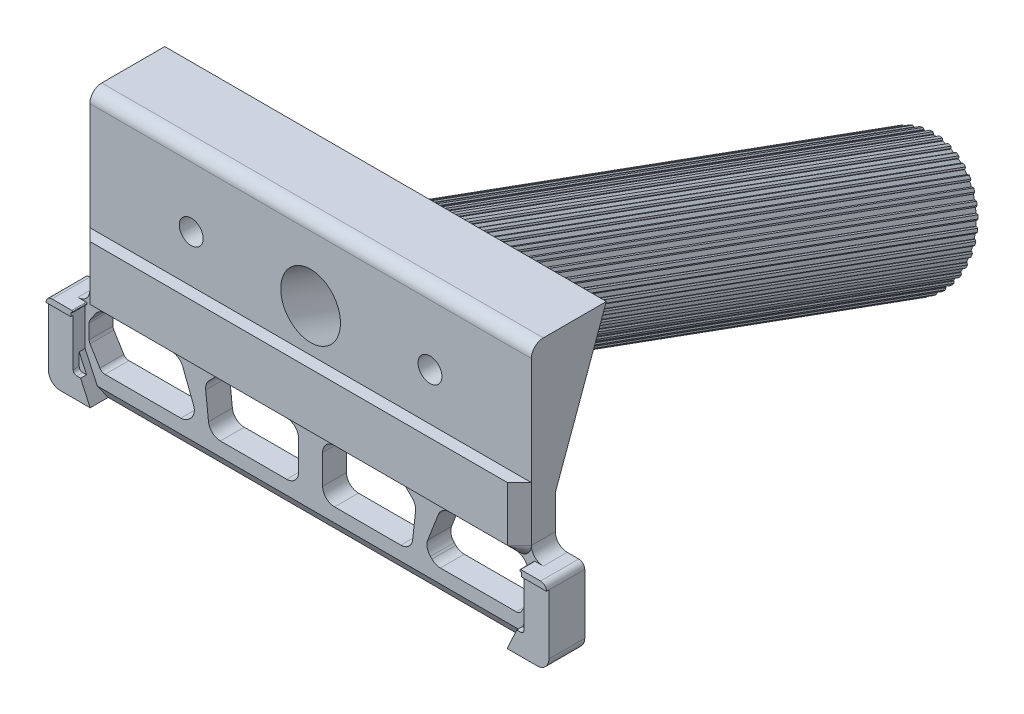
SolidWorks part; units mm, degrees
ref_plane "Front Plane" through (0, 0, 0) normal (0, 0, 1) x (1, 0, 0)
ref_plane "Top Plane" through (0, 0, 0) normal (0, 1, 0) x (1, 0, 0)
ref_plane "Right Plane" through (0, 0, 0) normal (1, 0, 0) x (0, 0, -1)
sketch "base plate" plane through (0, 0, 0) normal (0, 0, 1) x (1, 0, 0)
  line L0 (19.4937, 6.5) -> (20.4641, 6.5)
  line L1 (-18.4937, 12.0545) -> (-18.4937, 7.5)
  line L2 (20.9641, 6) -> (20.9641, 1)
  line L3 (19.9641, 0) -> (-19.9641, 0)
  line L4 (2.0062, 6.5) -> (7.9562, 6.5)
  line L5 (18.0111, 6.0574) -> (18.4651, 5.381)
  line L7 (18.4761, 3.6343) -> (17.6502, 2.2885)
  line L9 (18.4937, 7.5) -> (18.4937, 12.0545)
  line L10 (18.4937, 12.0545) -> (-18.4937, 12.0545)
  line L12 (18.55, 5.1023) -> (18.55, 3.8958)
  line L13 (7.558, 2.05) -> (2.0062, 2.05)
  line L14 (11.6407, 6.5) -> (17.1808, 6.5)
  line L16 (1.0062, 5.5) -> (1.0062, 3.05)
  line L21 (7.9562, 6.5) -> (8.5017, 5.9545)
  line L22 (8.7888, 5.1403) -> (8.5523, 2.943)
  line L23 (10.8704, 2.05) -> (17.2241, 2.05)
  line L24 (10.1633, 2.3429) -> (10.0333, 2.4728)
  line L25 (9.8082, 3.5417) -> (10.7085, 5.8618)
  line L31 (-9.8082, 3.5417) -> (-10.7085, 5.8618)
  line L33 (18.4937, 12.0545) -> (18.4937, 7.5)
  line L36 (-10.1633, 2.3429) -> (-10.0333, 2.4728)
  line L43 (0, 12.0545) -> (0, 0) construction
  line L44 (-10.8704, 2.05) -> (-17.2241, 2.05)
  line L45 (-8.7888, 5.1403) -> (-8.5523, 2.943)
  line L46 (-7.9562, 6.5) -> (-8.5017, 5.9545)
  line L47 (-1.0062, 5.5) -> (-1.0062, 3.05)
  line L48 (-11.6407, 6.5) -> (-17.1808, 6.5)
  line L49 (-7.558, 2.05) -> (-2.0062, 2.05)
  line L50 (-18.55, 5.1023) -> (-18.55, 3.8958)
  line L51 (-18.4937, 7.5) -> (-18.4937, 12.0545)
  line L52 (-18.4761, 3.6343) -> (-17.6502, 2.2885)
  line L53 (-18.0111, 6.0574) -> (-18.4651, 5.381)
  line L54 (-2.0062, 6.5) -> (-7.9562, 6.5)
  line L55 (-20.9641, 6) -> (-20.9641, 1)
  line L56 (-19.4937, 6.5) -> (-20.4641, 6.5)
  arc A0 (18.4937, 7.5) -> (19.4937, 6.5) centre (19.4937, 7.5) ccw
  arc A2 (17.2241, 2.05) -> (17.6502, 2.2885) centre (17.2241, 2.55) ccw
  arc A3 (18.4761, 3.6343) -> (18.55, 3.8958) centre (18.05, 3.8958) ccw
  arc A4 (18.4651, 5.381) -> (18.55, 5.1023) centre (18.05, 5.1023) cw
  arc A5 (20.9641, 6) -> (20.4641, 6.5) centre (20.4641, 6) ccw
  arc A6 (19.9641, 0) -> (20.9641, 1) centre (19.9641, 1) ccw
  arc A7 (7.558, 2.05) -> (8.5523, 2.943) centre (7.558, 3.05) ccw
  arc A8 (8.7888, 5.1403) -> (8.5017, 5.9545) centre (7.7946, 5.2474) ccw
  arc A9 (10.0333, 2.4728) -> (9.8082, 3.5417) centre (10.7404, 3.1799) cw
  arc A10 (10.1633, 2.3429) -> (10.8704, 2.05) centre (10.8704, 3.05) ccw
  arc A11 (11.6407, 6.5) -> (10.7085, 5.8618) centre (11.6407, 5.5) ccw
  arc A12 (2.0062, 2.05) -> (1.0062, 3.05) centre (2.0062, 3.05) cw
  arc A13 (2.0062, 6.5) -> (1.0062, 5.5) centre (2.0062, 5.5) ccw
  arc A29 (18.0111, 6.0574) -> (17.1808, 6.5) centre (17.1808, 5.5) ccw
  arc A30 (-18.0111, 6.0574) -> (-17.1808, 6.5) centre (-17.1808, 5.5) cw
  arc A31 (-2.0062, 6.5) -> (-1.0062, 5.5) centre (-2.0062, 5.5) cw
  arc A32 (-2.0062, 2.05) -> (-1.0062, 3.05) centre (-2.0062, 3.05) ccw
  arc A33 (-11.6407, 6.5) -> (-10.7085, 5.8618) centre (-11.6407, 5.5) cw
  arc A34 (-10.1633, 2.3429) -> (-10.8704, 2.05) centre (-10.8704, 3.05) cw
  arc A35 (-10.0333, 2.4728) -> (-9.8082, 3.5417) centre (-10.7404, 3.1799) ccw
  arc A36 (-8.7888, 5.1403) -> (-8.5017, 5.9545) centre (-7.7946, 5.2474) cw
  arc A37 (-7.558, 2.05) -> (-8.5523, 2.943) centre (-7.558, 3.05) cw
  arc A38 (-19.9641, 0) -> (-20.9641, 1) centre (-19.9641, 1) cw
  arc A39 (-20.9641, 6) -> (-20.4641, 6.5) centre (-20.4641, 6) cw
  arc A40 (-18.4651, 5.381) -> (-18.55, 5.1023) centre (-18.05, 5.1023) ccw
  arc A41 (-18.4761, 3.6343) -> (-18.55, 3.8958) centre (-18.05, 3.8958) cw
  arc A42 (-17.2241, 2.05) -> (-17.6502, 2.2885) centre (-17.2241, 2.55) cw
  arc A43 (-18.4937, 7.5) -> (-19.4937, 6.5) centre (-19.4937, 7.5) cw
  dimension "D3" = 4.45
  dimension "D7" = 0.5
  dimension "D6" = 20.9641
  dimension "D1" = 12.0545
  dimension "D2" = 2.05
  dimension "D4" = 6.5
  dimension "D8" = 0.4704
  dimension "D5" = 1
  dimension "D9" = 1
  dimension "D10" = 6.95
  dimension "D11" = 2.45
  dimension "D12" = 0.7715
  dimension "D16" = 10.8704
  dimension "D23" = 0.5
  dimension "D20" = 5.1023
  dimension "D13" = 7.9562
  dimension "D14" = 8.5017
  dimension "D15" = 8.5523
  dimension "D17" = 9.8082
  dimension "D18" = 3.5417
  dimension "D19" = 0.1838
  dimension "D21" = 3.6343
  dimension "D22" = 1.579
  dimension "D24" = 0.8146
  dimension "D25" = 18.0111
  dimension "D27" = 6.0574
extrude "Boss-Extrude3" add sketch "base plate" along normal blind 2 contours L3 A6 L2 A5 L0 A0 L9 L10 A29 L5 A4 L12 A3 L7 A2 L23 A10 L24 A9 L25 A11 L14 A13 L4 L21 A8 L22 A7 L13 A12 L16 | L43 L10 L1 A43 L56 A39 L55 A38 L3 L44 A42 L52 A41 L50 A40 L53 A30 L48 A33 L31 A35 L36 A34 L49 A37 L45 A36 L46 L54 A31 L47 A32 region at (10.051, 6.4857, 0) region at (-10.051, 6.4857, 0)
sketch "Sketch3" plane through (0, 0, 2) normal (0, 0, 1) x (1, 0, 0)
  line L16 (0, 0) -> (0, 12.0545) construction
  line L17 (18.4937, 12.0545) -> (-18.4937, 12.0545) construction
  line L18 (-18.4937, 12.0545) -> (18.4937, 12.0545)
  line L19 (18.4937, 12.0545) -> (18.4937, 7.5)
  line L20 (-17.4937, 6.5) -> (17.4937, 6.5)
  line L21 (2.0062, 6.5) -> (7.9562, 6.5) construction
  line L22 (-18.4937, 12.0545) -> (-18.4937, 7.5)
  arc A6 (17.4937, 6.5) -> (18.4937, 7.5) centre (17.4937, 7.5) ccw
  arc A7 (-17.4937, 6.5) -> (-18.4937, 7.5) centre (-17.4937, 7.5) cw
  point P16 (0, 6.5)
  dimension "D1" = 1
extrude "Boss-Extrude4" add sketch "Sketch3" along normal blind 1
sketch "pill" plane through (0, 0, 3) normal (0, 0, 1) x (1, 0, 0)
  line L14 (20.9641, 6) -> (18.8845, 6)
  line L19 (18.7281, 6.43) -> (18.7281, 6.4096)
  line L21 (18.7981, 6.3396) -> (18.8145, 6.3396)
  line L22 (19.4937, 6.5) -> (20.4641, 6.5) construction
  line L23 (18.7981, 6.5) -> (20.4641, 6.5)
  line L24 (18.8845, 6) -> (18.8845, 6.2696)
  line L26 (0, -1.1) -> (0, 1.1) construction
  line L27 (-18.8845, 6) -> (-18.8845, 6.2696)
  line L28 (-18.7981, 6.5) -> (-20.4641, 6.5)
  line L29 (-18.7981, 6.3396) -> (-18.8145, 6.3396)
  line L30 (-18.7281, 6.43) -> (-18.7281, 6.4096)
  line L31 (-20.9641, 6) -> (-18.8845, 6)
  arc A11 (18.7981, 6.5) -> (18.7281, 6.43) centre (18.7981, 6.43) ccw
  arc A12 (18.8145, 6.3396) -> (18.8845, 6.2696) centre (18.8145, 6.2696) cw
  arc A13 (18.7281, 6.4096) -> (18.7981, 6.3396) centre (18.7981, 6.4096) ccw
  arc A14 (20.9641, 6) -> (20.4641, 6.5) centre (20.4641, 6) ccw construction
  arc A15 (20.9641, 6) -> (20.4641, 6.5) centre (20.4641, 6) ccw
  arc A16 (-20.9641, 6) -> (-20.4641, 6.5) centre (-20.4641, 6) cw
  arc A17 (-18.7281, 6.4096) -> (-18.7981, 6.3396) centre (-18.7981, 6.4096) cw
  arc A18 (-18.8145, 6.3396) -> (-18.8845, 6.2696) centre (-18.8145, 6.2696) ccw
  arc A19 (-18.7981, 6.5) -> (-18.7281, 6.43) centre (-18.7981, 6.43) cw
  dimension "D4" = 0.0164
  dimension "D3" = 0.2696
  dimension "D1" = 0.07
  dimension "D2" = 18.7281
  dimension "D5" = 0.0204
extrude "pill extrude" add sketch "pill" against normal up to next and the other way blind 0.2 contours L21 | A19 L28 A16 L31 L27 A18 L29 A17 L30 region at (19.8486, 6.2466, 3) region at (-19.8486, 6.2466, 3)
sketch "pods" plane through (0, 0, 2) normal (0, 0, 1) x (1, 0, 0)
  line L2 (20.9641, 6) -> (18.8845, 6) construction
  line L6 (19.9641, 0) -> (-19.9641, 0) construction
  line L7 (20.9641, 6) -> (20.9641, 1) construction
  line L14 (20.9641, 6) -> (18.8845, 6)
  line L15 (19.9641, 0) -> (17.4641, 0)
  line L20 (20.9641, 6) -> (20.9641, 1)
  line L21 (18.8845, 6) -> (18.8845, 3.1)
  line L22 (18.8845, 3.1) -> (17.4641, 0)
  line L23 (0, 0) -> (0, 12.0545) construction
  line L24 (18.4937, 12.0545) -> (-18.4937, 12.0545) construction
  line L25 (-18.8845, 3.1) -> (-17.4641, 0)
  line L26 (-18.8845, 6) -> (-18.8845, 3.1)
  line L27 (-20.9641, 6) -> (-20.9641, 1)
  line L28 (-19.9641, 0) -> (-17.4641, 0)
  line L29 (-20.9641, 6) -> (-18.8845, 6)
  arc A0 (19.9641, 0) -> (20.9641, 1) centre (19.9641, 1) ccw construction
  arc A2 (19.9641, 0) -> (20.9641, 1) centre (19.9641, 1) ccw
  arc A3 (-19.9641, 0) -> (-20.9641, 1) centre (-19.9641, 1) cw
  dimension "D1" = 3.5
  dimension "D2" = 3.1
extrude "Boss-Extrude7" add sketch "pods" along normal blind 1 contours L15 A2 L20 L14 L21 L22 | A3 L28 L25 L26 L29 L27 region at (19.6819, 2.7419, 2) region at (-19.6819, 2.7419, 2)
sketch "Sketch6" plane through (0, 0, 0) normal (0, 0, 1) x (1, 0, 0)
  line L0 (-18.5845, 0) -> (18.5845, 0)
  line L1 (18.8845, 0.3) -> (18.8845, 6.2696)
  line L2 (18.7981, 6.5) -> (21.4, 6.5)
  line L3 (21.6, 6.7) -> (21.6, 10.8413)
  line L4 (21.6, 10.8413) -> (-21.6, 10.8413)
  line L5 (0, 10.8413) -> (0, 0) construction
  line L10 (18.7281, 6.43) -> (18.7281, 6.4096)
  line L11 (18.7981, 6.3396) -> (18.8145, 6.3396)
  line L12 (-18.7981, 6.3396) -> (-18.8145, 6.3396)
  line L13 (-18.7281, 6.43) -> (-18.7281, 6.4096)
  line L15 (-21.6, 6.7) -> (-21.6, 10.8413)
  line L16 (-18.7981, 6.5) -> (-21.4, 6.5)
  line L17 (-18.8845, 0.3) -> (-18.8845, 6.2696)
  line L18 (17.4641, 0) -> (-17.4641, 0) construction
  line L20 (-18.8845, 6) -> (-18.8845, 6.2696) construction
  line L21 (-18.7981, 6.5) -> (-20.4641, 6.5) construction
  line L22 (18.8845, 6) -> (18.8845, 6.2696) construction
  line L23 (-18.7281, 6.4096) -> (-18.7281, 6.43) construction
  arc A1 (18.5845, 0) -> (18.8845, 0.3) centre (18.5845, 0.3) ccw
  arc A2 (18.7981, 6.5) -> (18.7281, 6.43) centre (18.7981, 6.43) ccw
  arc A3 (18.8145, 6.3396) -> (18.8845, 6.2696) centre (18.8145, 6.2696) cw
  arc A4 (18.7281, 6.4096) -> (18.7981, 6.3396) centre (18.7981, 6.4096) ccw
  arc A5 (21.4, 6.5) -> (21.6, 6.7) centre (21.4, 6.7) ccw
  arc A6 (-21.4, 6.5) -> (-21.6, 6.7) centre (-21.4, 6.7) cw
  arc A7 (-18.7281, 6.4096) -> (-18.7981, 6.3396) centre (-18.7981, 6.4096) cw
  arc A8 (-18.8145, 6.3396) -> (-18.8845, 6.2696) centre (-18.8145, 6.2696) ccw
  arc A9 (-18.7981, 6.5) -> (-18.7281, 6.43) centre (-18.7981, 6.43) cw
  arc A10 (-18.5845, 0) -> (-18.8845, 0.3) centre (-18.5845, 0.3) cw
  dimension "D5" = 0.07
  dimension "D6" = 0.3
  dimension "D7" = 0.2
  dimension "D1" = 4.3413
  dimension "D3" = 21.6
sketch "Sketch7" plane through (0, 0, 3) normal (0, 0, 1) x (1, 0, 0)
  line L5 (-18.5845, 1.75) -> (18.5845, 1.75)
  line L16 (18.8845, 2.05) -> (18.8845, 6.2696)
  line L18 (0, 0) -> (0, 8.3662) construction
  line L19 (18.8845, 6.2696) -> (-18.8845, 6.2696)
  line L20 (18.8845, 6) -> (18.8845, 6.2696) construction
  line L21 (-18.8845, 2.05) -> (-18.8845, 6.2696)
  arc A10 (18.5845, 1.75) -> (18.8845, 2.05) centre (18.5845, 2.05) ccw
  arc A11 (-18.5845, 1.75) -> (-18.8845, 2.05) centre (-18.5845, 2.05) cw
  point P12 (0, 6.2696)
  point P13 (0, 1.75)
  dimension "D2" = 6.2696
  dimension "D3" = 0.3
  dimension "D1" = 4.5196
extrude "Cut-Extrude2" cut sketch "Sketch7" against normal blind 0.5
sketch "Sketch12" plane through (0, 0, 0) normal (1, 0, 0) x (0, 0, -1)
  line L0 (-2, 12.0545) -> (-2, 21.0545)
  line L4 (0, 10.3066) -> (4.2759, 22.0545)
  line L5 (-1, 22.0545) -> (4.2759, 22.0545)
  line L6 (-2, 12.0545) -> (0, 10.3066)
  line L7 (-3, 12.0545) -> (0, 12.0545) construction
  line L8 (0, 7.5) -> (0, 12.0545) construction
  arc A0 (-2, 21.0545) -> (-1, 22.0545) centre (-1, 21.0545) cw
  point P8 (-2, 22.0545)
  dimension "D2" = 1
  dimension "D1" = 10
  dimension "D3" = 11.7479
  dimension "D4" = 20
  dimension "D5" = 48.848
extrude "Boss-Extrude11" add sketch "Sketch12" along normal up to surface and the other way up to surface up to face at (18.4937, 9.3218, 1.6) other way up to face at (-18.4937, 9.3218, 1.6)
ref_plane "Plane1" through (0, 1.2056, 3.3125) normal (0, -0.342, -0.9397) x (-1, 0, 0)
sketch "Sketch28" plane through (0, 1.2056, 3.3125) normal (0, -0.342, -0.9397) x (-1, 0, 0)
  circle A0 centre (0, 14) radius 5
  circle A1 centre (0, 14) radius 2.5
  dimension "D1" = 10
  dimension "D2" = 5
  dimension "D3" = 14
extrude "Boss-Extrude12" add sketch "Sketch28" along normal blind 50 contours A0 A1 region at (4.8586, 14.3613, -1.4758)
sketch "Sketch30" plane through (0, -15.8954, -43.6722) normal (0, -0.342, -0.9397) x (-1, 0, 0)
  line L0 (0, 14) -> (5.1304, 13.5511)
  line L1 (0, 14) -> (5.15, 14)
  circle A0 centre (0, 14) radius 4.95
  circle A1 centre (0, 14) radius 5.15
  circle M4 centre (0, 14) radius 5
  dimension "D1" = 10.3
  dimension "D2" = 9.9
  dimension "D3" = 5
extrude "Boss-Extrude13" add sketch "Sketch30" against normal blind 45 contours L0 A1 L1 M4 region at (-5.0689, -2.9476, -48.3847)
chamfer "Chamfer3" distance 0.1 angle 45 2 edges at (-5.1304, 4.534, -27.1638) (-5.15, 4.9558, -27.3174) tangent propagation no
pattern_circular "CirPattern1" count 40 over 360 about axis through (0, -2.7397, -48.4604) along (0, -0.342, -0.9397) of "Boss-Extrude13", "Chamfer3"
sketch "Sketch31" plane through (0, 0, 0) normal (1, 0, 0) x (0, 0, -1)
  line L6 (-2.5, 1.75) -> (-0.8595, -1.0914)
  line L7 (-2.5, 1.75) -> (-4.2635, 1.75)
  line L8 (-4.2635, 1.75) -> (-4.2635, -1.0914)
  line L9 (-4.2635, -1.0914) -> (-0.8595, -1.0914)
  line L10 (-3, 0) -> (0, 0) construction
  dimension "D1" = 120
  dimension "D2" = 3.404
  dimension "D3" = 2.8414
extrude "Cut-Extrude11" cut sketch "Sketch31" along normal up to surface and the other way up to surface up to face at (18.2049, 1.6167, 2.5) other way up to face at (-18.2049, 1.6167, 2.5)
extrude "Cut-Extrude12" cut sketch "Sketch28<3>" against normal blind 14 contours A1 region at (0, 14.3613, -1.4758)
sketch "Sketch28<3>" plane through (0, 1.2056, 3.3125) normal (0, -0.342, -0.9397) x (-1, 0, 0) same geometry as "Sketch28"
ref_plane "Plane2" through (0, 0, 2) normal (0, 0, 1) x (1, 0, 0)
sketch "Sketch33" plane through (0, 0, 2) normal (0, 0, 1) x (1, 0, 0)
  line L0 (0, 0) -> (0, 24.2375) construction
  circle A0 centre (10, 16) radius 1
  circle A1 centre (-10, 16) radius 1
  dimension "D1" = 2
  dimension "D2" = 10
  dimension "D3" = 16
extrude "Cut-Extrude13" cut sketch "Sketch33" against normal blind 14
sketch "Sketch37" [suppressed] plane through (0, 0, 0) normal (1, 0, 0) x (0, 0, -1)
  line L0 (-3, 12.0545) -> (-2, 12.0545) construction
  line L1 (-2, 12.0545) -> (-2, 21.0545) construction
  line L2 (-3, 12.0545) -> (-2, 12.0545)
  line L3 (-2, 12.0545) -> (-2, 21.0545)
  line L4 (-3, 12.0545) -> (-3, 6.2696)
  line L5 (-2, 21.0545) -> (-6.3266, 21.0545)
  line L6 (-6.3266, 21.0545) -> (-6.3266, 12.0545)
  line L7 (-6.3266, 12.0545) -> (-6.3266, 6.8068)
  line L8 (-2.5, 1.75) -> (-3, 1.75) construction
  dimension "D1" = 10.3045
  dimension "D2" = 0.5
  dimension "D3" = 0.5
fillet "Chamfer5" radius 1 1 edges at (0, 6.5, 3) type face fillet profile chamfer first side face at (0, 8.6158, 3) second side face at (0, 6.5, 1.3)
sketch "Sketch38" plane through (0, 0, 3) normal (0, 0, 1) x (1, 0, 0)
  line L0 (-17.2885, 21.0545) -> (17.2885, 21.0545)
  line L1 (-17.2885, 7.5) -> (-17.2885, 4)
  line L2 (18.4937, 21.0545) -> (-18.4937, 21.0545) construction
  line L3 (17.2885, 21.0545) -> (17.2885, 7.5)
  line L4 (-17.4937, 7.5) -> (17.4937, 7.5) construction
  line L5 (17.2885, 7.5) -> (17.2885, 4)
  line L6 (17.2885, 4) -> (-17.2885, 4)
  line L7 (0, 21.0545) -> (0, 4) construction
  line L8 (-17.2885, 21.0545) -> (-17.2885, 7.5)
  dimension "D1" = 17.2885
  dimension "D2" = 3.5
sketch "Sketch39" [suppressed] plane through (0, 0, 2) normal (0, 0, 1) x (1, 0, 0)
  line L0 (-10, 16) -> (0, 16)
  line L1 (0, 21.0545) -> (0, 12.0545) construction
  line L2 (0, 16) -> (0, 12.0545)
  line L3 (18.4937, 12.0545) -> (-18.4937, 12.0545) construction
